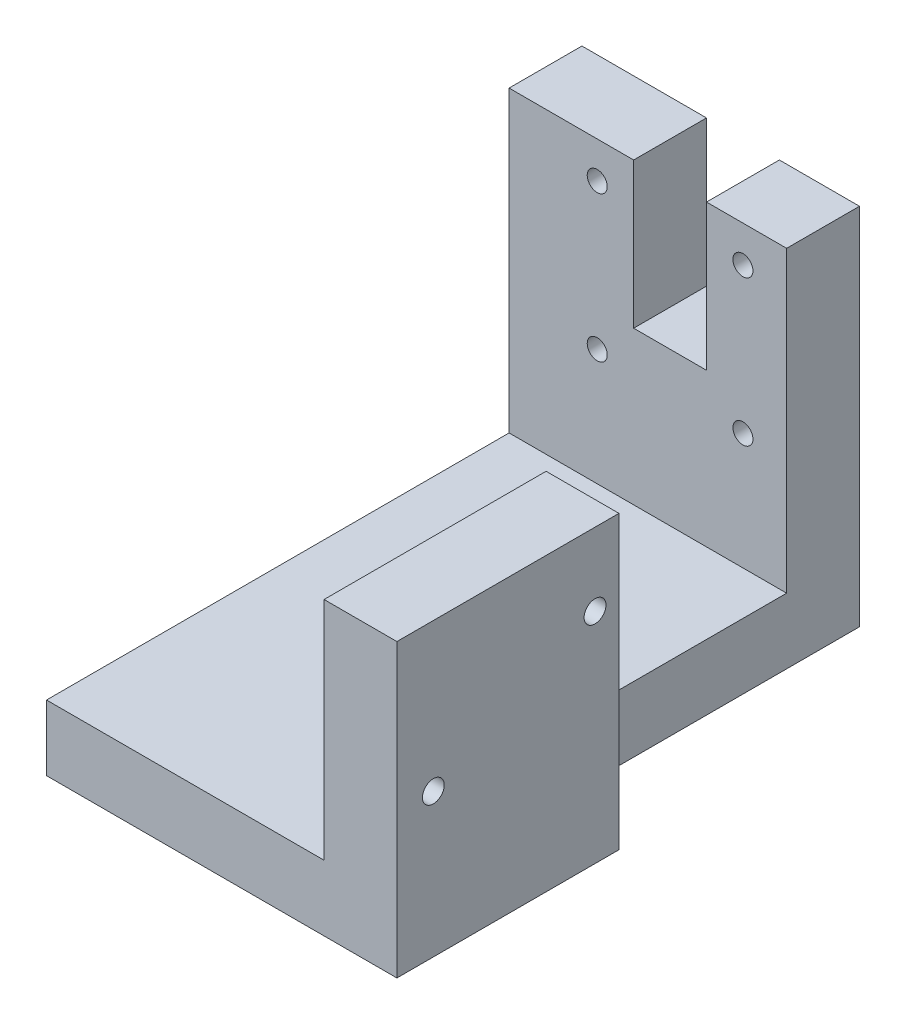
SolidWorks part; units mm, degrees
ref_plane "Front Plane" through (0, 0, 0) normal (0, 0, 1) x (1, 0, 0)
ref_plane "Top Plane" through (0, 0, 0) normal (0, 1, 0) x (1, 0, 0)
ref_plane "Right Plane" through (0, 0, 0) normal (1, 0, 0) x (0, 0, -1)
sketch "Sketch1" plane through (0, 0, 0) normal (0, 1, 0) x (1, 0, 0)
  line L0 (29.05, -1.27) -> (19.05, -1.27)
  line L1 (-19.05, 31.75) -> (19.05, 31.75)
  line L2 (-19.05, 31.75) -> (-19.05, -31.75)
  line L3 (-19.05, -31.75) -> (19.05, -31.75)
  line L4 (19.05, 31.75) -> (19.05, -31.75)
  line L6 (19.05, 31.75) -> (19.05, -31.75)
  line L7 (19.05, -31.75) -> (29.05, -31.75)
  line L8 (29.05, -1.27) -> (29.05, -31.75)
  circle A1 centre (0, -6.35) radius 4.064
  point P4 (0, 31.75)
  point P6 (-19.05, 0)
  dimension "D3" = 8.128
  dimension "D1" = 38.1
  dimension "D2" = 63.5
  dimension "D4" = 25.4
  dimension "D5" = 10
  dimension "D6" = 30.48
extrude "Boss-Extrude1" add sketch "Sketch1" along normal blind 9 contours L4 L1 L2 L3 A1 region at (0, 0, -0.1392)
extrude "Boss-Extrude2" add sketch "Sketch1<3>" along normal blind 40 contours L8 L4 L7 region at (24.05, 0, 16.51)
sketch "Sketch1<3>" plane through (0, 0, 0) normal (0, 1, 0) x (1, 0, 0) same geometry as "Sketch1"
ref_plane "Plane1" through (29.05, 0, 0) normal (1, 0, 0) x (0, 0, -1)
sketch "Sketch2" plane through (29.05, 0, 0) normal (1, 0, 0) x (0, 0, -1)
  line L0 (-31.75, 40) -> (-31.75, 0) construction
  line L2 (-1.27, 0) -> (-31.75, 0) construction
  circle A0 centre (-26.75, 19.7) radius 1.5
  circle A1 centre (-4.55, 30) radius 1.5
  dimension "D3" = 3
  dimension "D1" = 22.2
  dimension "D2" = 10.3
  dimension "D4" = 5
  dimension "D5" = 30
extrude "Cut-Extrude1" cut sketch "Sketch2" against normal blind 10
ref_plane "Plane2" through (0, 0, -31.75) normal (0, 0, -1) x (-1, 0, 0)
sketch "Sketch3" plane through (0, 0, -31.75) normal (0, 0, -1) x (-1, 0, 0)
  line L0 (-19.05, 40) -> (-19.05, 9) construction
  line L1 (19.05, 0) -> (-19.05, 0)
  line L2 (19.05, 0) -> (19.05, 50)
  line L3 (19.05, 50) -> (-19.05, 50)
  line L4 (-19.05, 0) -> (-19.05, 50)
  line L5 (-8.05, 50) -> (-8.05, 30)
  line L6 (-8.05, 30) -> (1.95, 30)
  line L7 (1.95, 30) -> (1.95, 50)
  circle A0 centre (-13.05, 45) radius 1.375
  circle A1 centre (6.95, 45) radius 1.375
  circle A2 centre (-13.05, 25) radius 1.375
  circle A3 centre (6.95, 25) radius 1.375
  point P16 (0, 0)
  dimension "D1" = 2.75
  dimension "D2" = 20
  dimension "D3" = 20
  dimension "D4" = 5
  dimension "D5" = 6
  dimension "D6" = 50
  dimension "D7" = 10
  dimension "D8" = 20
  dimension "D9" = 5
extrude "Boss-Extrude3" add sketch "Sketch3" along normal blind 10 contours L7 L6 L5 L3 L4 L1 L2 A3 A2 A1 A0 region at (-0.4059, 23.0743, -31.75)
